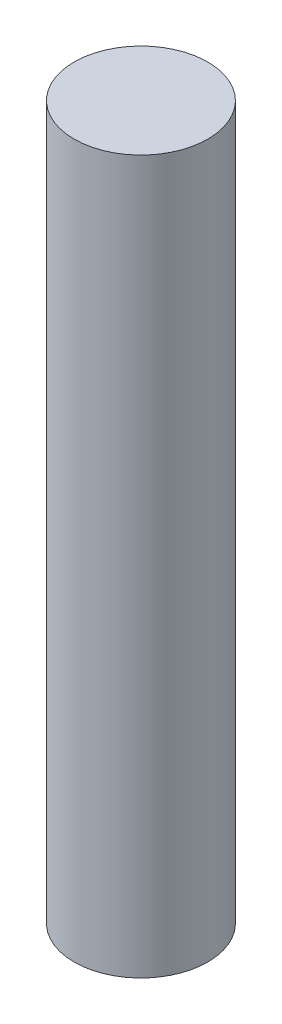
SolidWorks part; units mm, degrees
ref_plane "前视基准面" through (0, 0, 0) normal (0, 0, 1) x (1, 0, 0)
ref_plane "上视基准面" through (0, 0, 0) normal (0, 1, 0) x (1, 0, 0)
ref_plane "右视基准面" through (0, 0, 0) normal (1, 0, 0) x (0, 0, -1)
other "Configuration Table"
sketch "草图1" plane through (0, 0, 0) normal (0, 1, 0) x (1, 0, 0)
  line L5 (241.9495, -230.4137) -> (174.7692, -288.7901) construction
  line L6 (239.2741, -187.6955) -> (283.8763, -239.0243)
  line L10 (239.2741, -187.6955) -> (219.6484, -204.7493)
  line L11 (219.6484, -204.7493) -> (264.2506, -256.0781)
  line L12 (283.8763, -239.0243) -> (264.2506, -256.0781)
  line L13 (400, -400) -> (400, 400)
  line L14 (261.5752, -213.3599) -> (241.9495, -230.4137) construction
  line L15 (219.6484, -204.7493) -> (172.0938, -246.072) construction
  line L16 (152.4681, -263.1258) -> (197.0704, -314.4545)
  line L17 (197.0704, -314.4545) -> (216.6961, -297.4007)
  line L18 (216.6961, -297.4007) -> (172.0938, -246.072)
  line L19 (172.0938, -246.072) -> (152.4681, -263.1258)
  line L20 (162.281, -254.5989) -> (206.8832, -305.9276) construction
  line L21 (172.0938, -246.072) -> (264.2506, -256.0781) construction
  line L22 (218.1722, -251.075) -> (400, -400)
  line L24 (195.8711, -225.4106) -> (0, 0) construction
  line L25 (400, 0) -> (218.1722, -251.075)
  line L38 (0, -440) -> (0, 440) construction
  line L41 (-400, -400) -> (400, -400)
  line L42 (-400, 400) -> (400, 400)
  line L65 (-400, -400) -> (-400, 400)
  line L66 (274.0635, -247.5512) -> (229.4612, -196.2224) construction
  circle A0 centre (0, 0) radius 300
  circle A1 centre (0, 0) radius 150
  point P17 (174.7692, -288.7901)
  point P19 (218.1722, -251.075)
  point P20 (251.7624, -221.8868)
  point P21 (184.5821, -280.2632)
  point P22 (162.281, -254.5989)
  point P25 (229.4612, -196.2224)
  point P49 (-400, 0)
  dimension "D1" = 600
  dimension "D2" = 300
  dimension "D10" = 400
  dimension "D3" = 26
  dimension "D4" = 68
  dimension "D5" = 68
  dimension "D6" = 26
  dimension "D7" = 400
  dimension "D8" = 310
  dimension "D9" = 115
sketch "草图2" plane through (0, 0, 0) normal (0, 1, 0) x (1, 0, 0)
  circle A0 centre (0, 0) radius 150
  dimension "D1" = 300
extrude "凸台-拉伸1" add sketch "草图2" along normal blind 1500 and the other way blind 100
